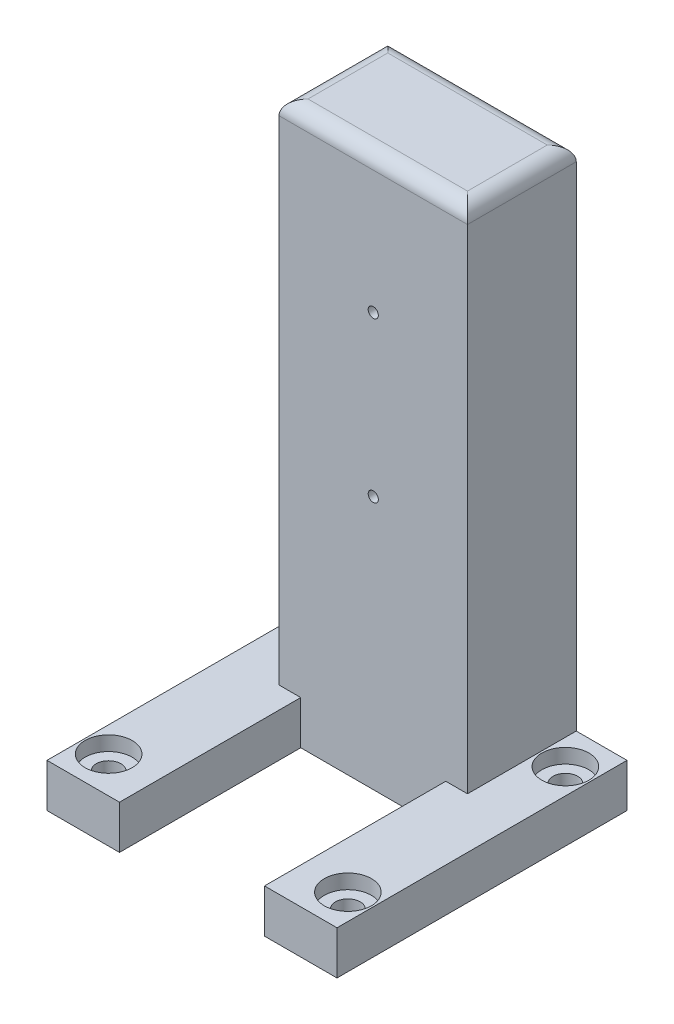
SolidWorks part; units mm, degrees
ref_plane "Plan de face" through (0, 0, 0) normal (0, 0, 1) x (1, 0, 0)
ref_plane "Plan de dessus" through (0, 0, 0) normal (0, 1, 0) x (1, 0, 0)
ref_plane "Plan de droite" through (0, 0, 0) normal (1, 0, 0) x (0, 0, -1)
sketch "Esquisse1" plane through (0, 0, 0) normal (0, 0, 1) x (1, 0, 0)
  line L0 (0, 0) -> (-20, 0)
  line L1 (-20, 0) -> (20, 0) construction
  line L2 (-20, 0) -> (-20, 76) construction
  line L3 (-20, 76) -> (20, 76) construction
  line L4 (20, 0) -> (20, 76) construction
  line L5 (-20, 0) -> (-20, 6)
  line L6 (-20, 6) -> (-13, 6)
  line L7 (-13, 6) -> (-13, 76)
  line L8 (-13, 76) -> (13, 76)
  line L9 (13, 76) -> (13, 6)
  line L10 (13, 6) -> (20, 6)
  line L11 (20, 6) -> (20, 0)
  line L12 (20, 0) -> (0, 0)
  point P4 (0, 0)
  dimension "D1" = 26
  dimension "D2" = 70
  dimension "D3" = 7
  dimension "D4" = 7
  dimension "D5" = 6
  dimension "D6" = 6
extrude "Boss.-Extru.1" add sketch "Esquisse1" along normal blind 15
sketch "Esquisse2" plane through (0, 0, 0) normal (0, -1, 0) x (1, 0, 0)
  line L1 (-20, 15) -> (20, 15) construction
  line L2 (-20, 15) -> (-20, 40) construction
  line L3 (-20, 40) -> (20, 40) construction
  line L4 (20, 15) -> (20, 40) construction
  line L5 (-20, 40) -> (-10, 40)
  line L6 (-20, 40) -> (-20, 15)
  line L7 (-20, 15) -> (-10, 15)
  line L8 (-10, 40) -> (-10, 15)
  line L9 (20, 40) -> (10, 40)
  line L10 (20, 40) -> (20, 15)
  line L11 (20, 15) -> (10, 15)
  line L12 (10, 40) -> (10, 15)
  dimension "D1" = 25
  dimension "D2" = 40
  dimension "D3" = 10
  dimension "D4" = 10
extrude "Boss.-Extru.2" add sketch "Esquisse2" against normal blind 6
sketch "Esquisse3" plane through (0, 0, 15) normal (0, 0, 1) x (1, 0, 0)
  line L0 (0, 76) -> (0, 0) construction
  line L1 (13, 76) -> (-13, 76) construction
  line L2 (-10, 0) -> (10, 0) construction
  circle A0 centre (0, 57) radius 1
  circle A1 centre (0, 35) radius 1
  dimension "D1" = 2
  dimension "D2" = 2
  dimension "D3" = 22
  dimension "D4" = 35
sketch "Esquisse4" plane through (0, 6, 0) normal (0, 1, 0) x (1, 0, 0)
  line L0 (-16.5, 0) -> (-16.5, -40) construction
  line L1 (-13, 0) -> (-20, 0) construction
  line L2 (16.5, 0) -> (16.5, -40) construction
  line L3 (20, 0) -> (13, 0) construction
  line L4 (-10, -40) -> (-20, -40) construction
  line L5 (20, -40) -> (10, -40) construction
  circle A0 centre (-16.5, -5) radius 1
  circle A1 centre (16.5, -5) radius 1
  circle A2 centre (16.5, -35) radius 1
  circle A3 centre (-16.5, -35) radius 1
  dimension "D1" = 2
  dimension "D2" = 2
  dimension "D3" = 2
  dimension "D4" = 2
  dimension "D5" = 5
  dimension "D6" = 5
  dimension "D7" = 5
  dimension "D8" = 5
hole_wizard "Dégagement M1.21" positions "Esquisse5" profile "Esquisse7" hole size "M1.2" standard "ISO" end condition through all
sketch "Esquisse5" plane through (0, 0, 15) normal (0, 0, 1) x (1, 0, 0)
  point P0 (0, 57)
  point P3 (0, 35)
sketch "Esquisse7" plane through (0, 57, 15) normal (1, 0, 0) x (0, -1, 0)
  line L0 (0, 0) -> (0, 15)
  line L1 (0, 15) -> (0.7, 15)
  line L2 (0.7, 15) -> (0.7, 0)
  line L5 (0.7, 0) -> (0, 0)
  line L11 (0, -6.35) -> (0, 107.95) construction
  dimension "Diamètre du perçage jusqu'au prochain" = 1.4
  dimension "Profondeur du perçage jusqu'au prochain" = 15
hole_wizard "Chambrage pour tête cylindrique fendue M31" positions "Esquisse8" profile "Esquisse9" counterbore size "M3" standard "ISO" end condition through all
sketch "Esquisse8" plane through (0, 6, 0) normal (0, 1, 0) x (1, 0, 0)
  point P0 (-16.5, -5)
  point P3 (16.5, -5)
  point P6 (16.5, -35)
  point P9 (-16.5, -35)
sketch "Esquisse9" plane through (-16.5, 6, 5) normal (1, 0, 0) x (0, 0, 1)
  line L0 (0, 0) -> (0, 6)
  line L1 (0, 6) -> (1.7, 6)
  line L3 (1.7, 6) -> (1.7, 2)
  line L4 (1.7, 2) -> (3.25, 2)
  line L5 (3.25, 2) -> (3.25, 0)
  line L7 (3.25, 0) -> (0, 0)
  line L11 (0, -6.35) -> (0, 107.95) construction
  dimension "Diamètre du perçage jusqu'au prochain" = 3.4
  dimension "Profondeur du perçage jusqu'au prochain" = 6
  dimension "Diamètre du chambrage" = 6.5
  dimension "Profondeur du chambrage" = 2
fillet "Congé1" radius 2 4 edges at (13, 76, 7.5) (0, 76, 15) (-13, 76, 7.5) (0, 76, 0)
equation "\"hauteur\"= 35'hauteur vis du bas"
equation "\"D4@Esquisse3\"=\"hauteur\""
